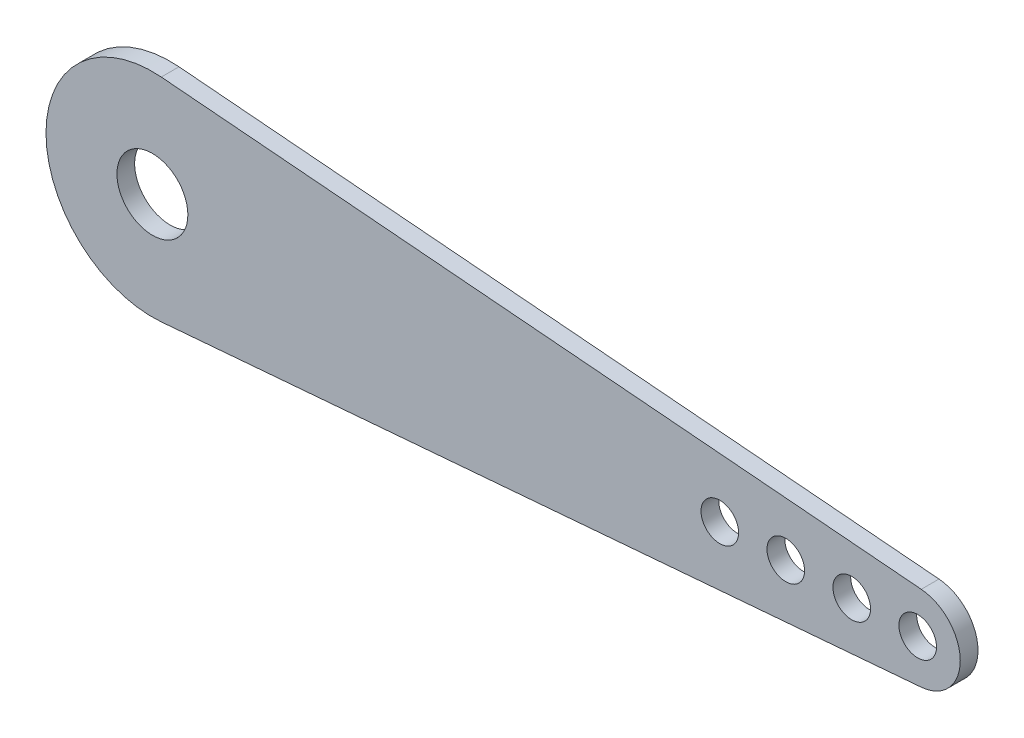
SolidWorks part; units mm, degrees
material "AISI 4340 Steel, normalized"
ref_plane "X-Y Datum" through (0, 0, 0) normal (0, 0, 1) x (1, 0, 0)
ref_plane "X-Z Datum" through (0, 0, 0) normal (0, 1, 0) x (1, 0, 0)
ref_plane "Y-Z Datum" through (0, 0, 0) normal (1, 0, 0) x (0, 0, -1)
sketch "Flat sketch" plane through (0, 0, 0) normal (0, 0, 1) x (1, 0, 0)
  line L0 (-6.35, 0) -> (137.033, 0) construction
  line L2 (1.589, 18.9836) -> (137.6686, 7.5934)
  line L3 (1.589, -18.9836) -> (137.6686, -7.5934)
  line L4 (137.6686, 7.5934) -> (137.6686, -7.5934) construction
  circle A0 centre (0, 0) radius 6.35
  circle A1 centre (0, 0) radius 19.05
  circle A2 centre (137.033, 0) radius 3.3655
  circle A8 centre (137.033, 0) radius 7.62
  circle A9 centre (125.222, 0) radius 3.3655
  circle A10 centre (113.411, 0) radius 3.3655
  circle A11 centre (101.6, 0) radius 3.3655
  point P5 (6.35, 0)
  point P9 (19.05, 0)
  point P10 (-19.05, 0)
  point P16 (144.653, 0)
  dimension "D1" = 12.7
  dimension "D2" = 38.1
  dimension "D3" = 6.731
  dimension "D7" = 15.24
  dimension "D6" = 11.811
  dimension "D8" = 163.703
  dimension "D5" = 101.6
  dimension "D4" = 4
extrude "Extrude face" add sketch "Flat sketch" along normal blind 3.175 contours A1 A0 | A8 A2 | A11 | A10 | A9 | A2 | A8 L2 A1 L3 A11 A10 A9 region at (64.3123, 0, 0) region at (13.6243, 12.5316, 0) region at (142.4827, 5.0126, 0) region at (137.033, 0, 0) region at (125.222, 0, 0) region at (113.411, 0, 0) region at (101.6, 0, 0)
extrude "Extrude cut - holes" cut sketch "Flat sketch<4>" along normal up to surface (3.175 mm away) contours A11 | A10 | A9 | A2 region at (137.033, 0, 0) region at (125.222, 0, 0) region at (113.411, 0, 0) region at (101.6, 0, 0) up to face at (6.35, 0, 3.175)
sketch "Flat sketch<4>" plane through (0, 0, 0) normal (0, 0, 1) x (1, 0, 0) same geometry as "Flat sketch"
equation "\"Torsion Bar O.D.\" = 0.5"
equation "\"Lever I.D. Torsion O.D. Clearance\"= 0"
equation "\"Lever I.D.\"= \"Torsion Bar O.D.\" + \"Lever I.D. Torsion O.D. Clearance\""
equation "\"D1@Flat sketch\" = \"Lever I.D.\""
equation "\"Lever O.D.\"= 1.5"
equation "\"D2@Flat sketch\" = \"Lever O.D.\""
equation "\"Lever Rod end I.D.\"= 0.265"
equation "\"D3@Flat sketch\" = \"Lever Rod end I.D.\""
equation "\"Distance b/w Lever Rod end holes\"= 0"
equation "\"Number of Lever Rod end holes\"= 0"
equation "\"Lever arc radius\"= 0.5"
equation "\"First Lever droplink hole length\" = 4"
equation "\"Lever thickness\"= 1 / 8in"
equation "\"D1@Extrude face\" = \"Lever thickness\""
equation "\"D5@Flat sketch\"=\"First Lever droplink hole length\""
